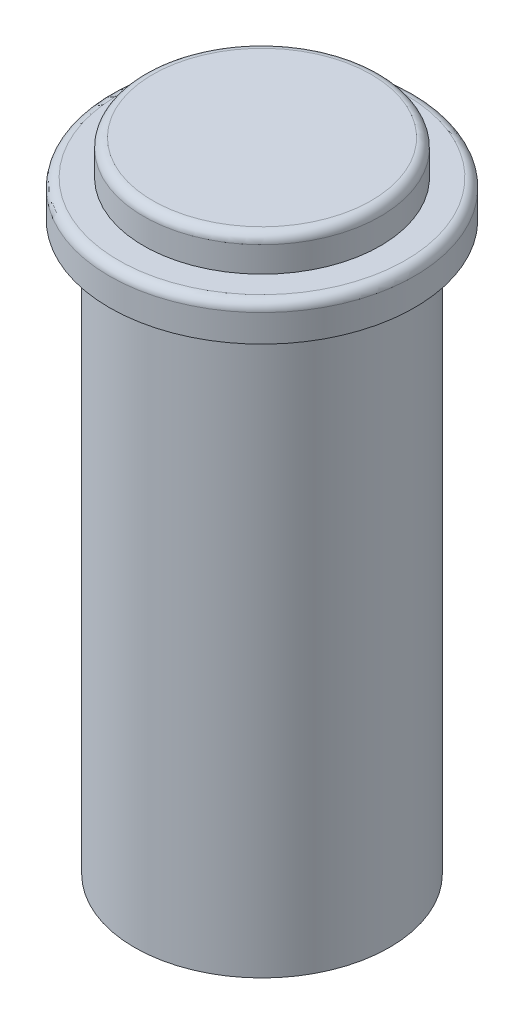
SolidWorks part; units mm, degrees
ref_plane "Front Plane" through (0, 0, 0) normal (0, 0, 1) x (1, 0, 0)
ref_plane "Top Plane" through (0, 0, 0) normal (0, 1, 0) x (1, 0, 0)
ref_plane "Right Plane" through (0, 0, 0) normal (1, 0, 0) x (0, 0, -1)
sketch "Sketch1" plane through (0, 0, 0) normal (0, 0, 1) x (1, 0, 0)
  line L0 (0, 0) -> (0, 75.2622) construction
  line L1 (0, 0) -> (-14, 0)
  line L2 (-14, 0) -> (-14, 62.2)
  line L3 (-14, 62.2) -> (-16.75, 62.2)
  line L4 (-16.75, 62.2) -> (-16.75, 66.2)
  line L5 (-16.75, 66.2) -> (-13, 66.2)
  line L6 (-13, 66.2) -> (-13, 70)
  line L7 (-13, 70) -> (0, 70)
  line L8 (0, 70) -> (0, 0)
  dimension "D1" = 70
  dimension "D2" = 7.8
  dimension "D3" = 4
  dimension "D4" = 28
  dimension "D5" = 33.5
  dimension "D6" = 26
revolve "Revolve1" add sketch "Sketch1" angle 360 about L0
fillet "Fillet1" radius 1 2 edges at (0, 70, -13) (0, 66.2, -16.75)
